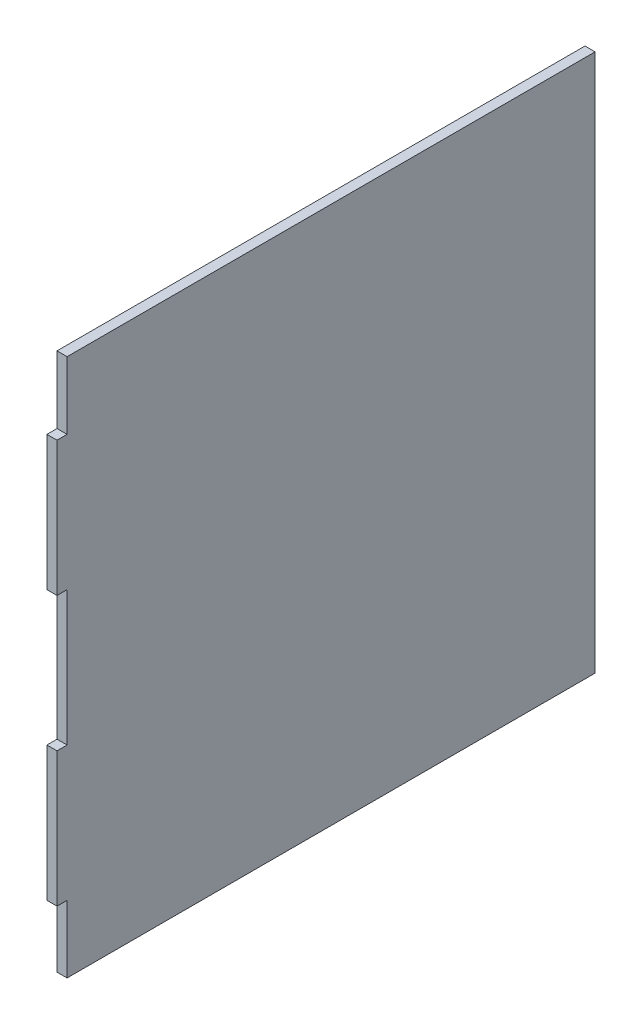
SolidWorks part; units mm, degrees
ref_plane "Front Plane" through (0, 0, 0) normal (0, 0, 1) x (1, 0, 0)
ref_plane "Top Plane" through (0, 0, 0) normal (0, 1, 0) x (1, 0, 0)
ref_plane "Right Plane" through (0, 0, 0) normal (1, 0, 0) x (0, 0, -1)
sketch "Sketch1" plane through (0, 0, 0) normal (1, 0, 0) x (0, 0, -1)
  line L1 (-80, 80) -> (80, 80)
  line L2 (-80, 80) -> (-80, -80)
  line L3 (-80, -80) -> (80, -80)
  line L4 (80, 80) -> (80, -80)
  line L5 (-80, 80) -> (80, -80) construction
  line L6 (-80, -80) -> (80, 80) construction
  point P0 (0, 0)
  dimension "D1" = 160
  dimension "D2" = 160
extrude "Boss-Extrude1" add sketch "Sketch1" along normal blind 3
sketch "Sketch2" plane through (3, 0, 0) normal (1, 0, 0) x (0, 0, -1)
  line L0 (-80, -60) -> (-77, -60)
  line L1 (-77, -60) -> (-77, -20)
  line L2 (-77, -20) -> (-80, -20)
  line L3 (-80, -20) -> (-80, 20)
  line L4 (-80, 20) -> (-77, 20)
  line L5 (-77, 20) -> (-77, 60)
  line L6 (-77, 60) -> (-80, 60)
  line L7 (-80, 60) -> (-80, -60)
  line L8 (-77, 20) -> (-77, -20)
  line L9 (0, 0) -> (77, 0) construction
  line L10 (80, 60) -> (77, 60)
  line L11 (77, 60) -> (77, 20)
  line L12 (77, 20) -> (80, 20)
  line L13 (80, 20) -> (80, -20)
  line L14 (80, -20) -> (77, -20)
  line L15 (77, -20) -> (77, -60)
  line L16 (77, -60) -> (80, -60)
  line L17 (80, -60) -> (80, 60)
  line L18 (77, 20) -> (77, -20)
  line L19 (0, 0) -> (-77, 0) construction
  line L20 (-80, 80) -> (-80, -80) construction
  line L21 (80, -80) -> (80, 80) construction
  line L22 (-77, 60) -> (-77, 80)
  line L23 (80, 80) -> (-80, 80) construction
  line L24 (-77, 80) -> (-80, 80)
  line L25 (-80, 80) -> (-80, 60)
  line L26 (-80, -60) -> (-80, -80)
  line L27 (-80, -80) -> (-77, -80)
  line L28 (-80, -80) -> (80, -80) construction
  line L29 (-77, -80) -> (-77, -60)
  line L30 (77, 60) -> (77, 80)
  line L31 (77, 80) -> (80, 80)
  line L32 (80, 80) -> (80, 60)
  line L33 (77, -60) -> (77, -80)
  line L34 (77, -80) -> (80, -80)
  line L35 (80, -80) -> (80, -60)
  line M7 (80, 80) -> (-80, 80)
  line M8 (-80, 80) -> (-80, -80)
  line M9 (-80, -80) -> (80, -80)
  dimension "D1" = 40
  dimension "D2" = 40
  dimension "3" = 3
  dimension "D4" = 40
  dimension "D5" = 3
  dimension "D6" = 40
extrude "Cut-Extrude1" cut sketch "Sketch2" against normal through all contours L6 L22 M7 M8 | L8 L4 L2 M8 | L29 L0 M9 M8 region at (3, -70, 78.5) region at (3, 0, 78.5) region at (3, 70, 78.5)
